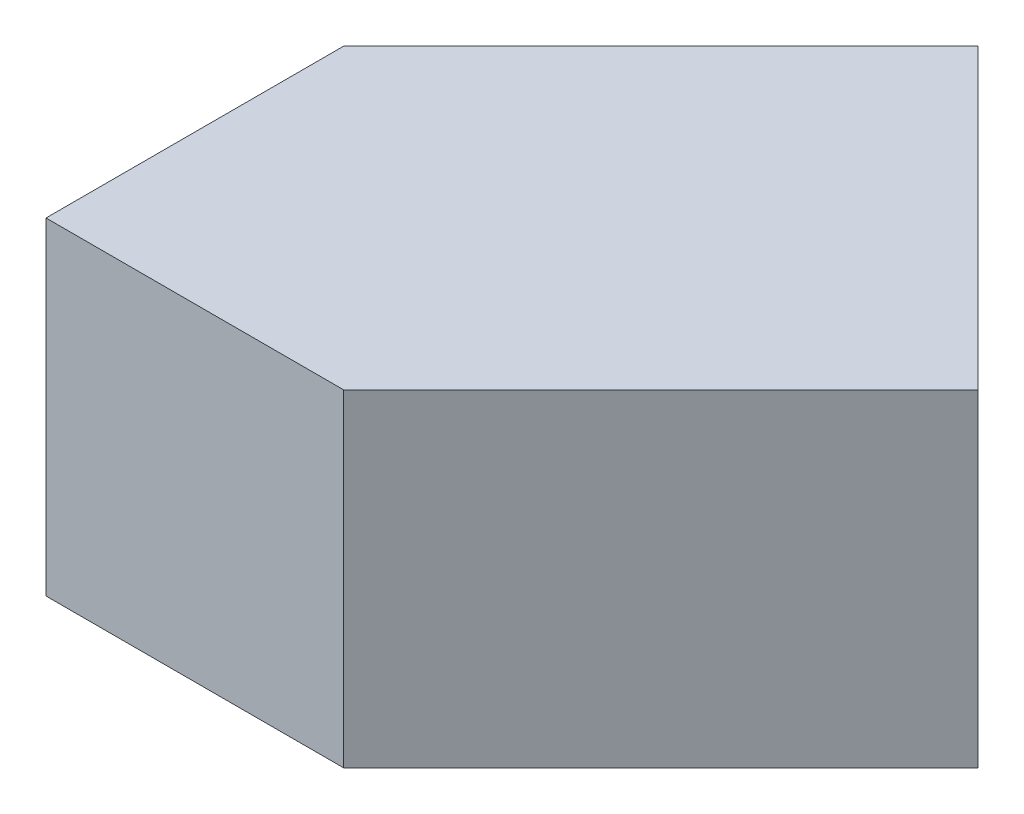
SolidWorks part; units mm, degrees
ref_plane "정면도" through (0, 0, 0) normal (0, 0, 1) x (1, 0, 0)
ref_plane "평면도" through (0, 0, 0) normal (0, 1, 0) x (1, 0, 0)
ref_plane "우측면도" through (0, 0, 0) normal (1, 0, 0) x (0, 0, -1)
sketch "스케치1" plane through (0, 0, 0) normal (0, 1, 0) x (1, 0, 0)
  line L1 (-10.1, -10.1) -> (10.1, -10.1)
  line L2 (-10.1, -10.1) -> (-10.1, 10.1)
  line L3 (-10.1, 10.1) -> (10.1, 10.1)
  line L4 (10.1, -10.1) -> (10.1, 10.1)
  line L5 (0, 10.1) -> (0, -10.1) construction
  line L6 (-10.1, 0) -> (10.1, 0) construction
  line L7 (-12.5, -12.5) -> (12.5, -12.5)
  line L8 (-12.5, -12.5) -> (-12.5, 12.5)
  line L9 (-12.5, 12.5) -> (12.5, 12.5)
  line L10 (12.5, -12.5) -> (12.5, 12.5)
  line L11 (0, 12.5) -> (0, -12.5) construction
  line L12 (-12.5, 0) -> (12.5, 0) construction
  point P0 (0, 0)
  point P4 (0, 0)
  dimension "D1" = 20.2
  dimension "D2" = 20.2
  dimension "D3" = 25
  dimension "D4" = 25
extrude "보스-돌출1" add sketch "스케치1" along normal blind 20 contours L7 L10 L9 L8 L4 L1 L2 L3 region at (-12.1464, 0, 0)
sketch "스케치2" plane through (0, 20, 0) normal (0, 1, 0) x (1, 0, 0)
  line L4 (-12.5, -12.5) -> (12.5, -12.5)
  line L5 (12.5, -12.5) -> (12.5, 12.5)
  line L6 (12.5, 12.5) -> (-12.5, 12.5)
  line L7 (-12.5, 12.5) -> (-12.5, -12.5)
  line L8 (-12.5, -12.5) -> (12.5, -12.5)
  line L9 (12.5, -12.5) -> (12.5, 12.5)
  line L10 (12.5, 12.5) -> (-12.5, 12.5)
  line L11 (-12.5, 12.5) -> (-12.5, -12.5)
  dimension "D1" = 0
extrude "보스-돌출2" add sketch "스케치2" along normal blind 7.5
ref_plane "평면1" through (0, 0, 0) normal (-0.7071, 0, 0.7071) x (0.7071, 0, 0.7071)
ref_plane "평면2" through (12.5, 0, -12.5) normal (-0.7071, 0, 0.7071) x (0.7071, 0, 0.7071)
sketch "스케치3" plane through (12.5, 0, -12.5) normal (-0.7071, 0, 0.7071) x (0.7071, 0, 0.7071)
  line L0 (0, 27.5) -> (0, 0) construction
  line L1 (17.6777, 0) -> (-17.6777, 0)
  line L2 (17.6777, 0) -> (17.6777, 27.5)
  line L3 (17.6777, 27.5) -> (-17.6777, 27.5)
  line L4 (-17.6777, 0) -> (-17.6777, 27.5)
  line L5 (0, 27.5) -> (0, 0) construction
  line L6 (17.6777, 13.75) -> (-17.6777, 13.75) construction
  line L8 (10.1, 3.65) -> (-10.1, 3.65)
  line L9 (10.1, 3.65) -> (10.1, 23.85)
  line L10 (10.1, 23.85) -> (-10.1, 23.85)
  line L11 (-10.1, 3.65) -> (-10.1, 23.85)
  line L12 (0, 23.85) -> (0, 3.65) construction
  line L13 (10.1, 13.75) -> (-10.1, 13.75) construction
  point P0 (0, 13.75)
  point P6 (0, 13.75)
  dimension "D1" = 20.2
  dimension "D2" = 20.2
extrude "보스-돌출3" add sketch "스케치3" along normal up to vertex (17.6777 mm away) and the other way blind 20 up to point (12.5, 27.5, 12.5)
extrude "컷-돌출1" cut sketch "스케치1<3>" along normal up to surface (23.85 mm away) contours L4 L3 L2 L1 up to face at (15.3001, 23.85, -15.3001)
sketch "스케치1<3>" plane through (0, 0, 0) normal (0, 1, 0) x (1, 0, 0) same geometry as "스케치1"
extrude "컷-돌출2" cut sketch "스케치3<2>" along normal blind 20 contours L10 L11 L8 L9
sketch "스케치3<2>" plane through (12.5, 0, -12.5) normal (-0.7071, 0, 0.7071) x (0.7071, 0, 0.7071) same geometry as "스케치3"
sketch "스케치4" plane through (12.5, 0, -12.5) normal (-0.7071, 0, 0.7071) x (0.7071, 0, 0.7071)
  line L0 (10.1, 3.65) -> (10.1, 23.85) construction
  line L1 (10.1, 3.65) -> (-10.1, 3.65) construction
  line L2 (10.1, 23.85) -> (-10.1, 23.85) construction
  line L3 (-10.1, 3.65) -> (-10.1, 23.85) construction
  line L4 (10.1, 3.65) -> (10.1, 23.85)
  line L5 (10.1, 3.65) -> (-10.1, 3.65)
  line L6 (10.1, 23.85) -> (-10.1, 23.85)
  line L7 (-10.1, 3.65) -> (-10.1, 23.85)
sketch "스케치5" plane through (0, 3.65, 0) normal (0, 1, 0) x (1, 0, 0)
  line L0 (19.6418, 5.3582) -> (5.3582, 19.6418) construction
  line L1 (19.6418, 5.3582) -> (5.3582, 19.6418)
  line L2 (10.1, 10.1) -> (10.1, -4.1836) construction
  line L3 (10.1, 10.1) -> (-4.1836, 10.1) construction
  line L4 (10.1, 10.1) -> (10.1, -4.1836)
  line L5 (10.1, 10.1) -> (-4.1836, 10.1)
  line L6 (33.7839, 19.5004) -> (10.1, -4.1836) construction
  line L7 (19.5004, 33.7839) -> (-4.1836, 10.1) construction
  line L8 (19.6418, 5.3582) -> (10.1, -4.1836)
  line L9 (5.3582, 19.6418) -> (-4.1836, 10.1)
extrude "보스-돌출4" add sketch "스케치5" along normal up to next
